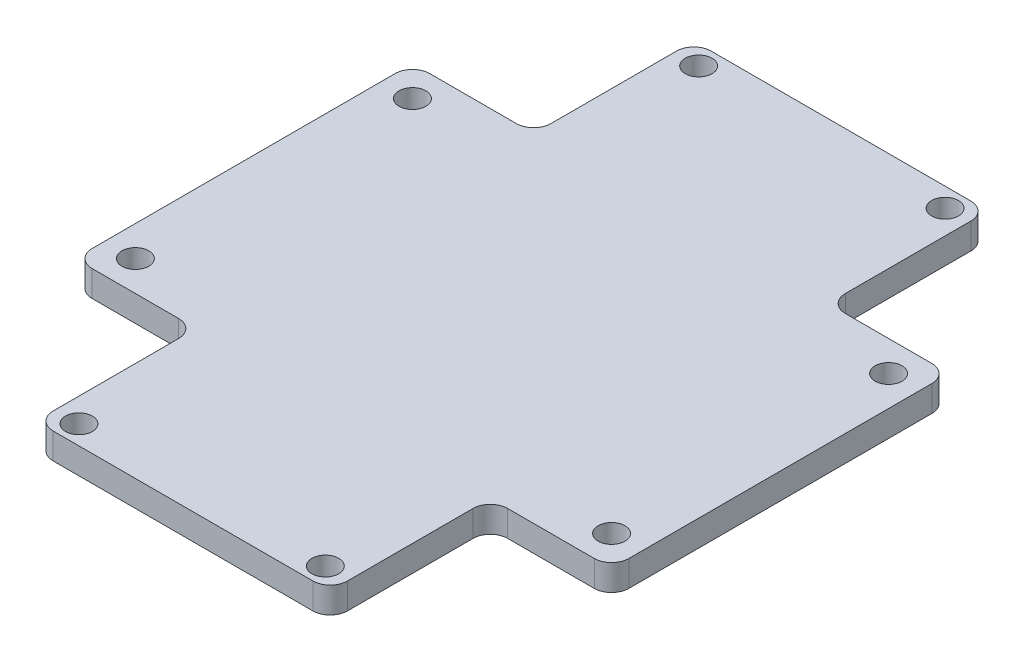
SolidWorks part; units mm, degrees
material "Thornel Mat VMA"
ref_plane "前视基准面" through (0, 0, 0) normal (0, 0, 1) x (1, 0, 0)
ref_plane "上视基准面" through (0, 0, 0) normal (0, 1, 0) x (1, 0, 0)
ref_plane "右视基准面" through (0, 0, 0) normal (1, 0, 0) x (0, 0, -1)
sketch "草图1" plane through (0, 0, 0) normal (0, 1, 0) x (1, 0, 0)
  line L1 (-31, 19.5) -> (31, 19.5)
  line L2 (-31, 19.5) -> (-31, -19.5)
  line L3 (-31, -19.5) -> (31, -19.5)
  line L4 (31, 19.5) -> (31, -19.5)
  line L5 (-31, 19.5) -> (31, -19.5) construction
  line L6 (-31, -19.5) -> (31, 19.5) construction
  line L7 (-27.5, 16) -> (27.5, 16) construction
  line L8 (-27.5, 16) -> (-27.5, -16) construction
  line L9 (-27.5, -16) -> (27.5, -16) construction
  line L10 (27.5, 16) -> (27.5, -16) construction
  line L11 (-27.5, 16) -> (27.5, -16) construction
  line L12 (-27.5, -16) -> (27.5, 16) construction
  line L13 (-14.23, 35.79) -> (14.23, 35.79) construction
  line L14 (-14.23, 35.79) -> (-14.23, -35.79) construction
  line L15 (-14.23, -35.79) -> (14.23, -35.79) construction
  line L16 (14.23, 35.79) -> (14.23, -35.79) construction
  line L17 (-14.23, 35.79) -> (14.23, -35.79) construction
  line L18 (-14.23, -35.79) -> (14.23, 35.79) construction
  line L19 (-17, 38) -> (17, 38)
  line L20 (-17, 38) -> (-17, -38)
  line L21 (-17, -38) -> (17, -38)
  line L22 (17, 38) -> (17, -38)
  line L23 (-17, 38) -> (17, -38) construction
  line L24 (-17, -38) -> (17, 38) construction
  circle A0 centre (-27.5, 16) radius 1.55
  circle A1 centre (27.5, 16) radius 1.55
  circle A2 centre (-27.5, -16) radius 1.55
  circle A3 centre (27.5, -16) radius 1.55
  circle A4 centre (-14.23, 35.79) radius 1.55
  circle A5 centre (14.23, 35.79) radius 1.55
  circle A6 centre (14.23, -35.79) radius 1.55
  circle A7 centre (-14.23, -35.79) radius 1.55
  point P0 (0, 0)
  point P6 (0, 0)
  point P15 (0, 0)
  point P20 (0, 0)
  dimension "D5" = 3.1
  dimension "D6" = 3.1
  dimension "D7" = 3.1
  dimension "D8" = 3.1
  dimension "D11" = 3.1
  dimension "D12" = 3.1
  dimension "D13" = 3.1
  dimension "D14" = 3.1
  dimension "D1" = 39
  dimension "D2" = 62
  dimension "D3" = 32
  dimension "D4" = 55
  dimension "D9" = 28.46
  dimension "D10" = 71.58
  dimension "D15" = 34
  dimension "D16" = 76
extrude "凸台-拉伸1" add sketch "草图1" along normal blind 3 contours L22 L19 L20 L1 A5 A4 | L22 L1 L20 L3 | L20 L1 L2 L3 A2 A0 | L22 L3 L20 L21 A7 A6 | L1 L22 L3 L4 A3 A1 region at (-23.9005, 0, 0) region at (0, 0, -28.5769) region at (0, 0, 0) region at (23.9005, 0, 0) region at (0, 0, 28.5769)
fillet "圆角1" radius 2 12 edges at (-31, 1.5, -19.5) (31, 1.5, -19.5) (31, 1.5, 19.5) (-31, 1.5, 19.5) (17, 1.5, 38) (-17, 1.5, 38) (-17, 1.5, 19.5) (17, 1.5, 19.5) (17, 1.5, -19.5) (-17, 1.5, -19.5) (17, 1.5, -38) (-17, 1.5, -38)
